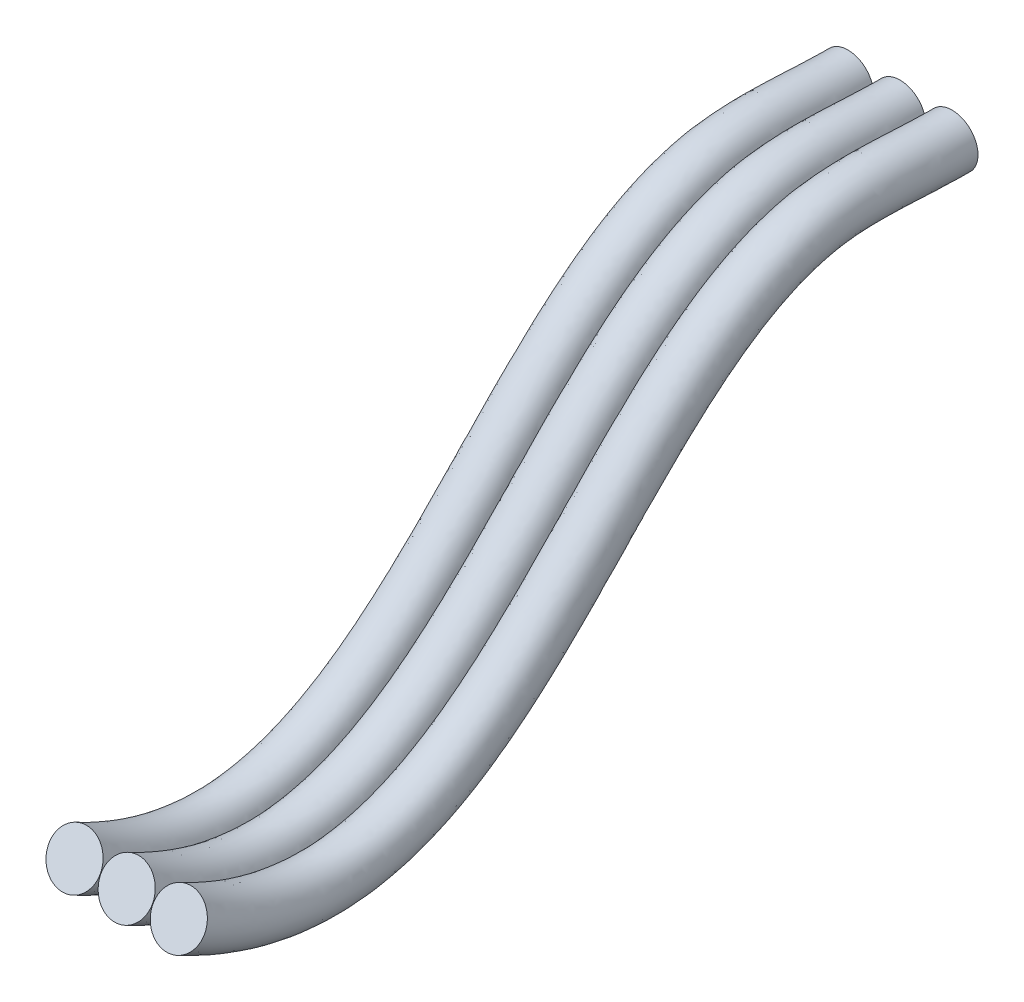
SolidWorks part; units mm, degrees
ref_plane "Front Plane" through (0, 0, 0) normal (0, 0, 1) x (1, 0, 0)
ref_plane "Top Plane" through (0, 0, 0) normal (0, 1, 0) x (1, 0, 0)
ref_plane "Right Plane" through (0, 0, 0) normal (1, 0, 0) x (0, 0, -1)
sketch "Sketch2" plane through (0, 0, 0) normal (1, 0, 0) x (0, 0, -1)
  line L1 (0, 3.8) -> (0, 7) construction
  spline S0 degree 3 poles (0, 5.4) (-1.3743, 5.4014) (-10.4185, 6.6895) (-14.2154, -8.6498) (-23.9233, -3.5067) knots 0 0 0 0 0.155478 1 1 1 1
sketch "Sketch3" plane through (0, 0, 0) normal (0, 0, 1) x (1, 0, 0)
  line L0 (0, 3.8) -> (0, 7) construction
  line L2 (-2.45, 6.4974) -> (-2.45, 4.303) construction
  line L3 (-2.45, 6.5) -> (-2.45, 4.3) construction
  line L6 (1.6127, 5.4) -> (-1.6127, 5.4) construction
  circle A0 centre (0, 5.4) radius 0.8
  circle A1 centre (-1.6127, 5.4) radius 0.8
  circle A2 centre (1.6127, 5.4) radius 0.8
  dimension "D1" = 0.0127
  dimension "D2" = 0.0127
  dimension "D3" = 1.6
sweep "Sweep2" add profiles "Sketch3" path "Sketch2"
